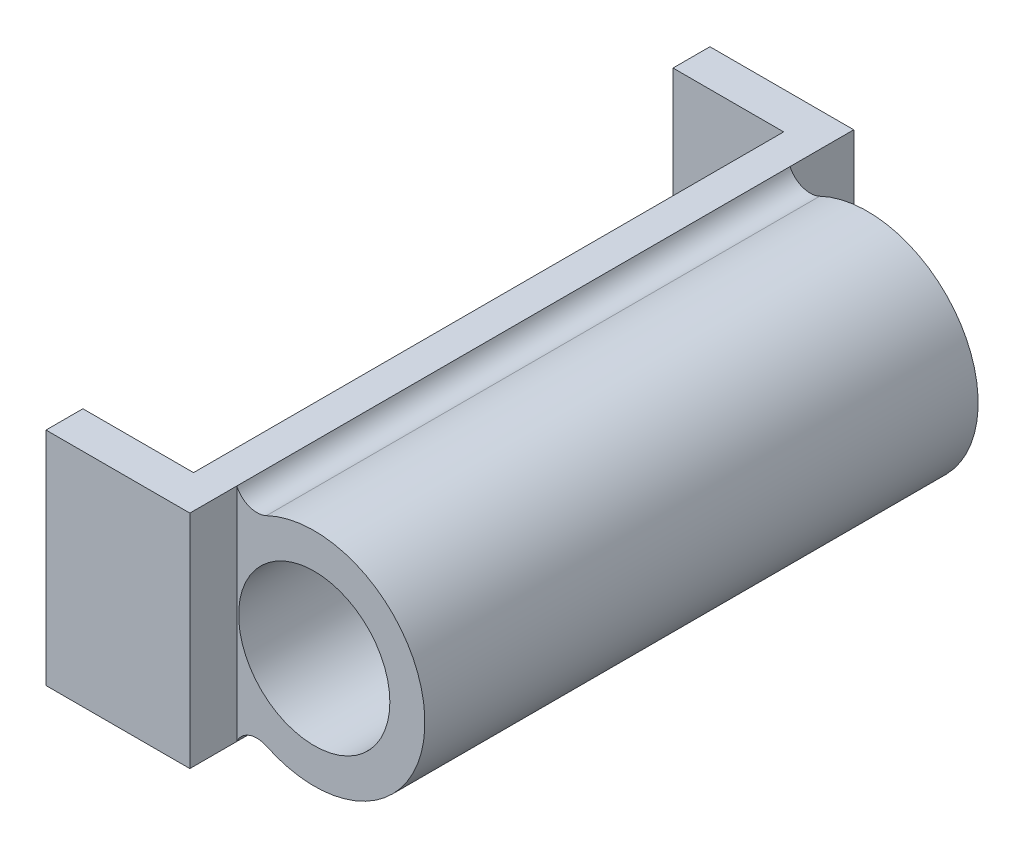
SolidWorks part; units mm, degrees
ref_plane "정면" through (0, 0, 0) normal (0, 0, 1) x (1, 0, 0)
ref_plane "윗면" through (0, 0, 0) normal (0, 1, 0) x (1, 0, 0)
ref_plane "우측면" through (0, 0, 0) normal (1, 0, 0) x (0, 0, -1)
sketch "스케치1" plane through (0, 0, 0) normal (0, 0, 1) x (1, 0, 0)
  line L1 (15, -15) -> (-15, -15)
  line L2 (15, -15) -> (15, 15)
  line L3 (15, 15) -> (-15, 15)
  line L4 (-15, -15) -> (-15, 15)
  line L5 (15, -15) -> (-15, 15) construction
  line L6 (15, 15) -> (-15, -15) construction
  circle A0 centre (0, 0) radius 9.8074
  dimension "D1" = 30
  dimension "D2" = 30
extrude "보스-돌출1" add sketch "스케치1" along normal blind 60
sketch "스케치2" plane through (0, -15, 0) normal (0, -1, 0) x (1, 0, 0)
  line L1 (15, 60) -> (-15, 60)
  line L2 (15, 60) -> (15, 90)
  line L3 (15, 90) -> (-15, 90)
  line L4 (-15, 60) -> (-15, 90)
  circle A0 centre (0, 75) radius 10.25
  dimension "D1" = 30
extrude "보스-돌출2" add sketch "스케치2" along normal blind 50 separate body
ref_plane "평면1" through (-15, -15, 60) normal (1, 0, 0) x (0, 0, -1)
sketch "스케치4" plane through (-15, -15, 60) normal (1, 0, 0) x (0, 0, -1)
  line L0 (-30, 0) -> (0, 0)
  line L1 (0, 0) -> (0, 30)
  arc A0 (-30, 0) -> (0, 30) centre (0, 0) cw
sketch "스케치6" plane through (0, 0, 60) normal (0, 0, 1) x (1, 0, 0)
  circle A0 centre (0, 0) radius 10.25
extrude "컷-돌출1" cut sketch "스케치6" against normal blind 60
sketch "스케치7" plane through (0, -15, 0) normal (0, 1, 0) x (1, 0, 0)
  line L1 (15, -90) -> (-15, -90)
  line L2 (15, -90) -> (15, -60)
  line L3 (15, -60) -> (-15, -60)
  line L4 (-15, -90) -> (-15, -60)
  circle A0 centre (0, -75) radius 10.25
revolve "회전1" add sketch "스케치7" angle 90 about L3
fillet "필렛2" radius 15 10 edges at (-15, -15, 30) (15, -15, 30) (-15, 15, 30) (-15, 6.2132, 81.2132) (15, 6.2132, 81.2132) (15, 15, 30) (-15, -40, 90) (15, -40, 90) (-15, -40, 60) (15, -40, 60)
sketch "스케치9" plane through (15, 0, 0) normal (1, 0, 0) x (0, 0, -1)
  line L0 (-45, 0) -> (-60, 0) construction
  line L1 (-27.2736, 70.9673) -> (-92.7264, 70.9673)
  line L2 (-27.2736, 70.9673) -> (-27.2736, -70.9673)
  line L3 (-27.2736, -70.9673) -> (-92.7264, -70.9673)
  line L4 (-92.7264, 70.9673) -> (-92.7264, -70.9673)
  line L5 (-27.2736, 70.9673) -> (-92.7264, -70.9673) construction
  line L6 (-27.2736, -70.9673) -> (-92.7264, 70.9673) construction
  arc A0 (-60, 0) -> (-75, -15) centre (-60, -15) ccw construction
  point P0 (-60, 0)
extrude "컷-돌출3" cut sketch "스케치9" against normal blind 30
sketch "스케치11" plane through (0, 0, 0) normal (0, 0, -1) x (-1, 0, 0)
  line L1 (-30, 16.5) -> (30, 16.5)
  line L2 (-30, 16.5) -> (-30, 13.5)
  line L3 (-30, 13.5) -> (30, 13.5)
  line L4 (30, 16.5) -> (30, 13.5)
  line L5 (-30, 16.5) -> (30, 13.5) construction
  line L6 (-30, 13.5) -> (30, 16.5) construction
  line L7 (30, 13.5) -> (-30, 13.5)
  line L8 (30, 13.5) -> (30, 10.5)
  line L9 (30, 10.5) -> (-30, 10.5)
  line L10 (-30, 13.5) -> (-30, 10.5)
  point P0 (0, 15)
  dimension "D1" = 60
  dimension "D2" = 3
  dimension "D3" = 3
ref_plane "평면3" through (0, 15, 27.2736) normal (0, 0, -1) x (-1, 0, 0)
sketch "스케치19" plane through (-15, -15, 60) normal (1, 0, 0) x (0, 0, -1)
  line L0 (32.7264, 15) -> (60, 15) construction
  line L1 (1.3632, 45) -> (91.3632, 45)
  line L2 (1.3632, 45) -> (1.3632, -15)
  line L3 (1.3632, -15) -> (91.3632, -15)
  line L4 (91.3632, 45) -> (91.3632, -15)
  line L5 (1.3632, 45) -> (91.3632, -15) construction
  line L6 (1.3632, -15) -> (91.3632, 45) construction
  point P0 (46.3632, 15)
  dimension "D1" = 90
  dimension "D2" = 60
extrude "보스-돌출9" add sketch "스케치19" along normal blind 4.5
sketch "스케치20" plane through (-15, 0, 0) normal (-1, 0, 0) x (0, 0, 1)
  line L0 (-31.3632, 30) -> (58.6368, 30) construction
  line L1 (58.6368, -30) -> (53.6368, -30)
  line L2 (58.6368, -30) -> (58.6368, 30)
  line L3 (58.6368, 30) -> (53.6368, 30)
  line L4 (53.6368, -30) -> (53.6368, 30)
  line L6 (-31.3632, -30) -> (-26.3632, -30)
  line L7 (-31.3632, -30) -> (-31.3632, 30)
  line L8 (-31.3632, 30) -> (-26.3632, 30)
  line L9 (-26.3632, -30) -> (-26.3632, 30)
  dimension "D1" = 5
  dimension "D2" = 5
extrude "보스-돌출10" add sketch "스케치20" along normal blind 15
sketch "스케치22" plane through (0, 0, 27.2736) normal (0, 0, 1) x (1, 0, 0)
  circle A0 centre (0, 0) radius 10.25
  circle A1 centre (0, 0) radius 15
extrude "보스-돌출11" add sketch "스케치22" along normal blind 25 and the other way blind 50
sketch "스케치26" plane through (-10.5, 0, 0) normal (1, 0, 0) x (0, 0, -1)
  line L0 (-58.6368, 30) -> (-58.6368, -30) construction
  line L1 (31.3632, -30) -> (-58.6368, -30)
  line L2 (31.3632, -30) -> (31.3632, -15)
  line L3 (31.3632, -15) -> (-58.6368, -15)
  line L4 (-58.6368, -30) -> (-58.6368, -15)
  line L6 (31.3632, 30) -> (-58.6368, 30)
  line L7 (31.3632, 30) -> (31.3632, 15)
  line L8 (31.3632, 15) -> (-58.6368, 15)
  line L9 (-58.6368, 30) -> (-58.6368, 15)
  dimension "D1" = 15
  dimension "D2" = 15
extrude "컷-돌출4" cut sketch "스케치26" against normal blind 20
fillet "필렛4" radius 3 2 edges at (-10.5, 10.7121, 14.7736) (-10.5, -10.7121, 14.7736)
